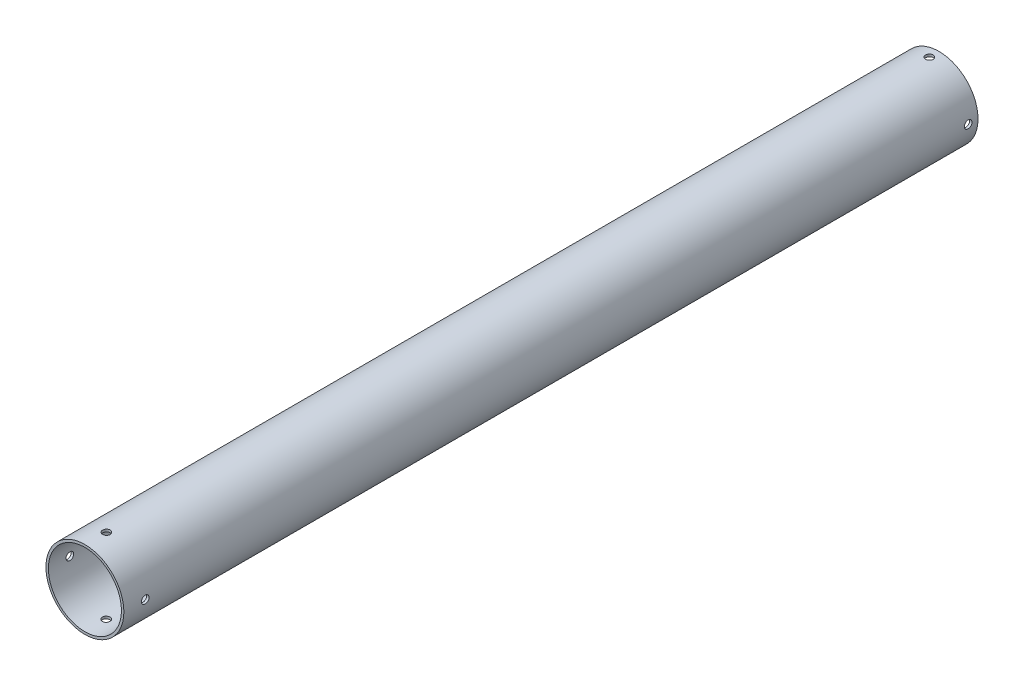
SolidWorks part; units mm, degrees
material "PC High Viscosity"
ref_plane "Front Plane" through (0, 0, 0) normal (0, 0, 1) x (1, 0, 0)
ref_plane "Top Plane" through (0, 0, 0) normal (0, 1, 0) x (1, 0, 0)
ref_plane "Right Plane" through (0, 0, 0) normal (1, 0, 0) x (0, 0, -1)
sketch "Sketch1" plane through (0, 0, 0) normal (0, 0, 1) x (1, 0, 0)
  circle A0 centre (0, 0) radius 23.8125
  circle A1 centre (0, 0) radius 25.4
  dimension "D1" = 50.8
  dimension "D2" = 47.625
extrude "Boss-Extrude1" add sketch "Sketch1" along normal mid plane 556.685
sketch "Sketch2" plane through (0, 0, 0) normal (1, 0, 0) x (0, 0, -1)
  line L0 (278.3425, -25.4) -> (278.3425, 25.4) construction
  circle A1 centre (271.9925, 0) radius 2.4892
  dimension "D1" = 4.9784
  dimension "D2" = 6.35
extrude "Cut-Extrude1" cut sketch "Sketch2" against normal through all both and the other way through all
sketch "Sketch3" plane through (0, 0, 0) normal (0, 1, 0) x (1, 0, 0)
  line L0 (25.4, 278.3425) -> (-25.4, 278.3425) construction
  circle A0 centre (0, 271.9925) radius 2.4892
  dimension "D1" = 4.9784
  dimension "D2" = 6.35
extrude "Cut-Extrude2" cut sketch "Sketch3" against normal through all both and the other way through all
sketch "Sketch4" plane through (0, 0, 0) normal (1, 0, 0) x (0, 0, -1)
  line L0 (-278.3425, 25.4) -> (-278.3425, -25.4) construction
  circle A0 centre (-264.3725, 0) radius 2.4892
  point P2 (0, 0)
  point P4 (-249.1052, 0)
  dimension "D1" = 13.97
  dimension "D2" = 4.9784
extrude "Cut-Extrude3" cut sketch "Sketch4" against normal through all both and the other way through all contours A0
sketch "Sketch5" plane through (0, 0, 0) normal (0, 1, 0) x (1, 0, 0)
  line L0 (-25.4, -278.3425) -> (25.4, -278.3425) construction
  circle A0 centre (0, -264.3725) radius 2.4892
  point P4 (0, 0)
  dimension "D1" = 4.9784
  dimension "D2" = 13.97
extrude "Cut-Extrude4" cut sketch "Sketch5" against normal through all both and the other way through all
equation "\"D1@Boss-Extrude1\"=21.125in+3.625mm"
